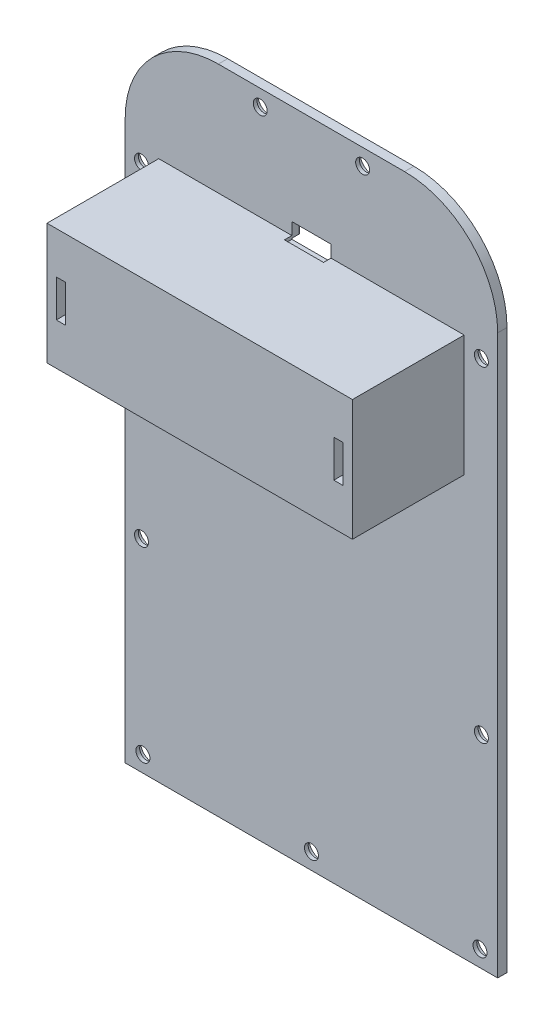
SolidWorks part; units mm, degrees
ref_plane "Alzado" through (0, 0, 0) normal (0, 0, 1) x (1, 0, 0)
ref_plane "Planta" through (0, 0, 0) normal (0, 1, 0) x (1, 0, 0)
ref_plane "Vista lateral" through (0, 0, 0) normal (1, 0, 0) x (0, 0, -1)
sketch "Croquis1" plane through (0, 0, 0) normal (0, 0, 1) x (1, 0, 0)
  line L1 (-19.9162, 25.8355) -> (20.0838, 25.8355)
  line L2 (-19.9162, 25.8355) -> (-19.9162, -44.1645)
  line L3 (-19.9162, -44.1645) -> (20.0838, -44.1645)
  line L4 (20.0838, 25.8355) -> (20.0838, -44.1645)
  dimension "D1" = 40
  dimension "D2" = 70
extrude "Saliente-Extruir1" add sketch "Croquis1" along normal blind 1
fillet "Redondeo1" radius 10 2 edges at (-19.9162, 25.8355, 0.5) (20.0838, 25.8355, 0.5)
sketch "Croquis2" plane through (0, 0, 0) normal (0, 0, -1) x (-1, 0, 0)
  line L54 (-10.0838, 25.8355) -> (9.9162, 25.8355) construction
  line L55 (-20.0838, -44.1645) -> (-20.0838, 15.8355) construction
  line L56 (19.9162, 15.8355) -> (19.9162, -44.1645) construction
  line L57 (19.9162, -44.1645) -> (-20.0838, -44.1645) construction
  circle A9 centre (-5.5838, 24.0855) radius 0.75
  circle A10 centre (5.4162, 24.0855) radius 0.75
  circle A11 centre (-18.1838, -42.4145) radius 0.75
  circle A12 centre (-0.0838, -42.4145) radius 0.75
  circle A13 centre (18.0162, -42.4145) radius 0.75
  circle A14 centre (-18.3338, 12.5855) radius 0.75
  circle A15 centre (-18.3338, -22.4145) radius 0.75
  circle A16 centre (18.1662, 12.5855) radius 0.75
  circle A17 centre (18.1662, -22.4145) radius 0.75
  point P34 (-0.0838, -44.1645)
  dimension "D1" = 1.5
  dimension "D2" = 1.75
  dimension "D3" = 14.5
  dimension "D4" = 14.5
  dimension "D5" = 1.75
  dimension "D6" = 1.75
  dimension "D7" = 1.75
  dimension "D8" = 1.9
  dimension "D9" = 1.9
  dimension "D10" = 20
  dimension "D11" = 35
extrude "Cortar-Extruir1" cut sketch "Croquis2" against normal up to next
sketch "Croquis5" plane through (0, 0, 1) normal (0, 0, 1) x (1, 0, 0)
  line L0 (-19.9162, -44.1645) -> (20.0838, -44.1645) construction
  line L1 (-16.3162, 13.8355) -> (16.4838, 13.8355)
  line L2 (-16.3162, 13.8355) -> (-16.3162, 0.8355)
  line L3 (-16.3162, 0.8355) -> (16.4838, 0.8355)
  line L4 (16.4838, 13.8355) -> (16.4838, 0.8355)
  point P6 (0.0838, -44.1645)
  point P7 (0.0838, 0.8355)
  dimension "D1" = 45
  dimension "D2" = 13
  dimension "D3" = 32.8
extrude "Saliente-Extruir2" add sketch "Croquis5" along normal blind 12
shell "Vaciado1" thickness 1 removed face at (-18.7662, -42.4145, 0)
sketch "Croquis6" plane through (0, 0, 12) normal (0, 0, -1) x (-1, 0, 0)
  line L0 (-15.4838, 1.8355) -> (-15.4838, 12.8355) construction
  line L1 (-15.4838, 9.3355) -> (-14.4838, 9.3355)
  line L2 (-15.4838, 9.3355) -> (-15.4838, 5.3355)
  line L3 (-15.4838, 5.3355) -> (-14.4838, 5.3355)
  line L4 (-14.4838, 9.3355) -> (-14.4838, 5.3355)
  line L5 (15.3162, 12.8355) -> (15.3162, 1.8355) construction
  line L6 (15.3162, 9.3355) -> (14.3162, 9.3355)
  line L7 (15.3162, 9.3355) -> (15.3162, 5.3355)
  line L8 (15.3162, 5.3355) -> (14.3162, 5.3355)
  line L9 (14.3162, 9.3355) -> (14.3162, 5.3355)
  line L10 (-15.4838, 1.8355) -> (-15.4838, 12.8355) construction
  point P12 (-15.4838, 7.3355)
  point P15 (15.3162, 7.3355)
  dimension "D1" = 1
  dimension "D2" = 4
extrude "Cortar-Extruir4" cut sketch "Croquis6" against normal up to next
sketch "Croquis7" plane through (0, 0, 0) normal (0, 0, -1) x (-1, 0, 0)
  line L0 (-15.4838, 12.8355) -> (15.3162, 12.8355) construction
  line L1 (-16.2338, 13.5855) -> (16.0662, 13.5855)
  line L2 (-16.2338, 13.5855) -> (-16.2338, 1.0855)
  line L3 (-16.2338, 1.0855) -> (16.0662, 1.0855)
  line L4 (16.0662, 13.5855) -> (16.0662, 1.0855)
  line L5 (15.3162, 1.8355) -> (-15.4838, 1.8355) construction
  line L6 (-15.4838, 1.8355) -> (-15.4838, 12.8355) construction
  line L7 (15.3162, 12.8355) -> (15.3162, 1.8355) construction
  dimension "D1" = 0.75
  dimension "D2" = 0.75
  dimension "D3" = 0.75
  dimension "D4" = 0.75
extrude "Cortar-Extruir5" cut sketch "Croquis7" against normal blind 1
sketch "Croquis8" plane through (0, 0, 0) normal (0, 0, -1) x (-1, 0, 0)
  line L0 (16.0662, 13.5855) -> (-16.2338, 13.5855) construction
  line L1 (-2.1838, 13.5855) -> (2.0162, 13.5855)
  line L2 (-2.1838, 13.5855) -> (-2.1838, 17.5855)
  line L3 (-2.1838, 17.5855) -> (2.0162, 17.5855)
  line L4 (2.0162, 13.5855) -> (2.0162, 17.5855)
  point P6 (-0.0838, 13.5855)
  dimension "D1" = 4.2
  dimension "D2" = 4
extrude "Cortar-Extruir6" cut sketch "Croquis8" against normal blind 0.6
fillet "Redondeo2" radius 1 2 edges at (-2.0162, 17.5855, 0.3) (2.1838, 17.5855, 0.3)
fillet "Redondeo3" radius 0.3 5 edges at (-2.0162, 15.0855, 0) (-1.7233, 17.2927, 0) (2.1838, 15.0855, 0) (1.8909, 17.2927, 0) (0.0838, 17.5855, 0)
sketch "Croquis9" plane through (0, 0, 0.6) normal (0, 0, -1) x (-1, 0, 0)
  line L0 (-2.1838, 16.5855) -> (-2.1838, 13.5855) construction
  line L1 (-2.1838, 15.1355) -> (2.0162, 15.1355)
  line L2 (-2.1838, 15.1355) -> (-2.1838, 13.4855)
  line L3 (-2.1838, 13.4855) -> (2.0162, 13.4855)
  line L4 (2.0162, 15.1355) -> (2.0162, 13.4855)
  line L5 (2.0162, 13.5855) -> (2.0162, 16.5855) construction
  line L6 (16.0662, 13.5855) -> (-16.2338, 13.5855) construction
  line L7 (-2.1838, 13.5855) -> (2.0162, 13.5855) construction
  dimension "D1" = 1.55
  dimension "D2" = 0.1
extrude "Cortar-Extruir7" cut sketch "Croquis9" against normal blind 1.2
sketch "Croquis10" plane through (0, 1.0855, 0) normal (0, 1, 0) x (1, 0, 0)
  line L1 (-14.0662, -0.5) -> (-12.0662, -0.5)
  line L2 (-14.0662, -0.5) -> (-14.0662, -1)
  line L3 (-14.0662, -1) -> (-12.0662, -1)
  line L4 (-12.0662, -0.5) -> (-12.0662, -1)
  line L5 (-16.0662, -1) -> (-16.0662, 0) construction
  line L6 (12.2338, -0.5) -> (14.2338, -0.5)
  line L7 (12.2338, -0.5) -> (12.2338, -1)
  line L8 (12.2338, -1) -> (14.2338, -1)
  line L9 (14.2338, -0.5) -> (14.2338, -1)
  line L10 (16.2338, -1) -> (16.2338, 0) construction
  line L11 (16.2338, -1) -> (-16.0662, -1) construction
  dimension "D1" = 2
  dimension "D2" = 2
  dimension "D3" = 0.5
  dimension "D4" = 2
extrude "Cortar-Extruir8" cut sketch "Croquis10" against normal blind 1.5
sketch "Croquis11" plane through (0, 0, 0) normal (0, 0, -1) x (-1, 0, 0)
  circle A0 centre (-5.5838, 24.0855) radius 1.25
  circle A1 centre (5.4162, 24.0855) radius 1.25
  circle A2 centre (18.1662, 12.5855) radius 1.25
  circle A3 centre (-18.3338, 12.5855) radius 1.25
  circle A4 centre (-18.3338, -22.4145) radius 1.25
  circle A5 centre (18.1662, -22.4145) radius 1.25
  circle A6 centre (18.0162, -42.4145) radius 1.25
  circle A7 centre (-0.0838, -42.4145) radius 1.25
  circle A8 centre (-18.1838, -42.4145) radius 1.25
  dimension "D1" = 2.5
extrude "Cortar-Extruir9" cut sketch "Croquis11" against normal blind 0.6 contours A0 | A1 | A3 | A2 | A4 | A5 | A8 | A7 | A6
sketch "Croquis12" plane through (0, 0, 1) normal (0, 0, -1) x (-1, 0, 0)
  line L0 (-15.4838, 12.8355) -> (15.3162, 12.8355) construction
  line L1 (-14.9838, 12.8355) -> (-14.4838, 12.8355)
  line L2 (-14.9838, 12.8355) -> (-14.9838, 10.8355)
  line L3 (-14.9838, 10.8355) -> (-14.4838, 10.8355)
  line L4 (-14.4838, 12.8355) -> (-14.4838, 10.8355)
  line L5 (-15.4838, 1.8355) -> (15.3162, 1.8355) construction
  line L6 (-14.9838, 1.8355) -> (-14.4838, 1.8355)
  line L7 (-14.9838, 1.8355) -> (-14.9838, 3.8355)
  line L8 (-14.9838, 3.8355) -> (-14.4838, 3.8355)
  line L9 (-14.4838, 1.8355) -> (-14.4838, 3.8355)
  line L10 (15.3162, 12.8355) -> (-15.4838, 12.8355) construction
  line L11 (14.8162, 12.8355) -> (14.3162, 12.8355)
  line L12 (14.8162, 12.8355) -> (14.8162, 10.8355)
  line L13 (14.8162, 10.8355) -> (14.3162, 10.8355)
  line L14 (14.3162, 12.8355) -> (14.3162, 10.8355)
  line L15 (15.3162, 1.8355) -> (-15.4838, 1.8355) construction
  line L16 (14.8162, 1.8355) -> (14.3162, 1.8355)
  line L17 (14.8162, 1.8355) -> (14.8162, 3.8355)
  line L18 (14.8162, 3.8355) -> (14.3162, 3.8355)
  line L19 (14.3162, 1.8355) -> (14.3162, 3.8355)
  line L20 (-15.4838, 12.8355) -> (-15.4838, 1.8355) construction
  line L21 (-15.4838, 1.8355) -> (-15.4838, 5.3355) construction
  line L22 (15.3162, 1.8355) -> (15.3162, 12.8355) construction
  dimension "D1" = 0.5
  dimension "D2" = 2
  dimension "D3" = 0.5
  dimension "D4" = 0.5
  dimension "D5" = 0.5
  dimension "D6" = 0.5
extrude "Saliente-Extruir3" add sketch "Croquis12" against normal up to next contours L2 L1 L4 L3 | L7 L6 L9 L8 | L12 L11 L14 L13 | L17 L16 L19 L18
